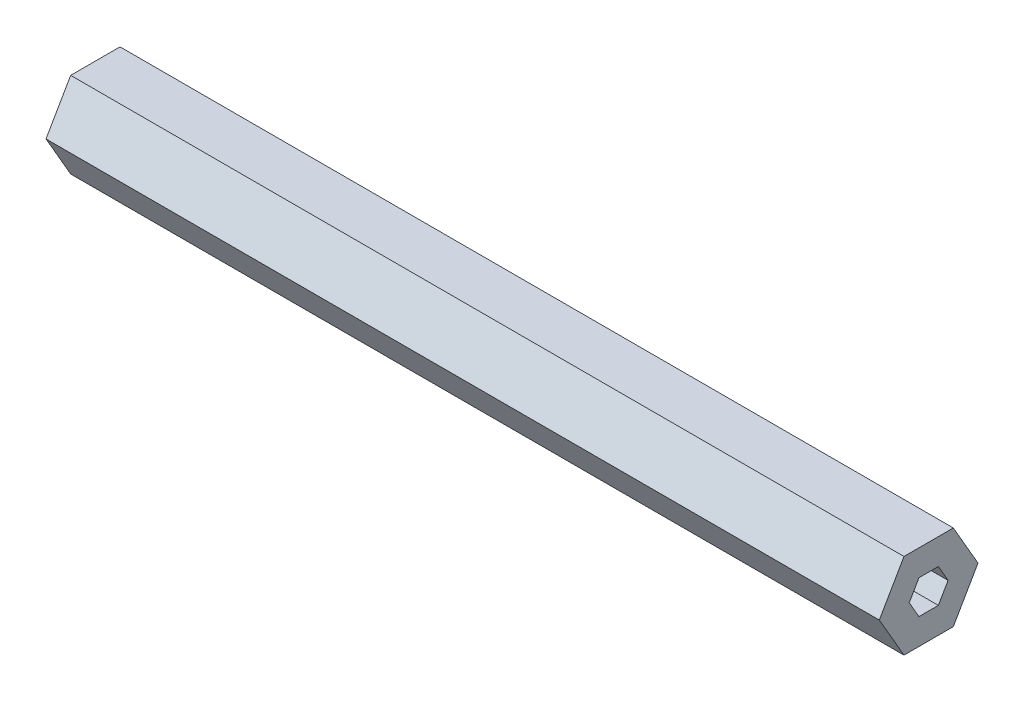
SolidWorks part; units mm, degrees
material "6061-T6 (SS)"
ref_plane "Front" through (0, 0, 0) normal (0, 0, 1) x (1, 0, 0)
ref_plane "Top" through (0, 0, 0) normal (0, 1, 0) x (1, 0, 0)
ref_plane "Right" through (0, 0, 0) normal (1, 0, 0) x (0, 0, -1)
sketch "Sketch1" plane through (0, 0, 0) normal (1, 0, 0) x (0, 0, -1)
  line L1 (7.3323, 0) -> (3.6662, 6.35)
  line L2 (3.6662, 6.35) -> (-3.6662, 6.35)
  line L3 (-3.6662, 6.35) -> (-7.3323, 0)
  line L4 (-7.3323, 0) -> (-3.6662, -6.35)
  line L5 (-3.6662, -6.35) -> (3.6662, -6.35)
  line L6 (3.6662, -6.35) -> (7.3323, 0)
  line L7 (2.8868, 0) -> (1.4434, 2.5)
  line L8 (1.4434, 2.5) -> (-1.4434, 2.5)
  line L9 (-1.4434, 2.5) -> (-2.8868, 0)
  line L10 (-2.8868, 0) -> (-1.4434, -2.5)
  line L11 (-1.4434, -2.5) -> (1.4434, -2.5)
  line L12 (1.4434, -2.5) -> (2.8868, 0)
  circle A0 centre (0, 0) radius 6.35 construction
  circle A1 centre (0, 0) radius 2.5 construction
  dimension "D1" = 12.7
  dimension "D2" = 5
extrude "Boss-Extrude1" add sketch "Sketch1" along normal mid plane 123.825
ref_axis "Axis1" through (-80.9, 0, 0) along (1, 0, 0)
